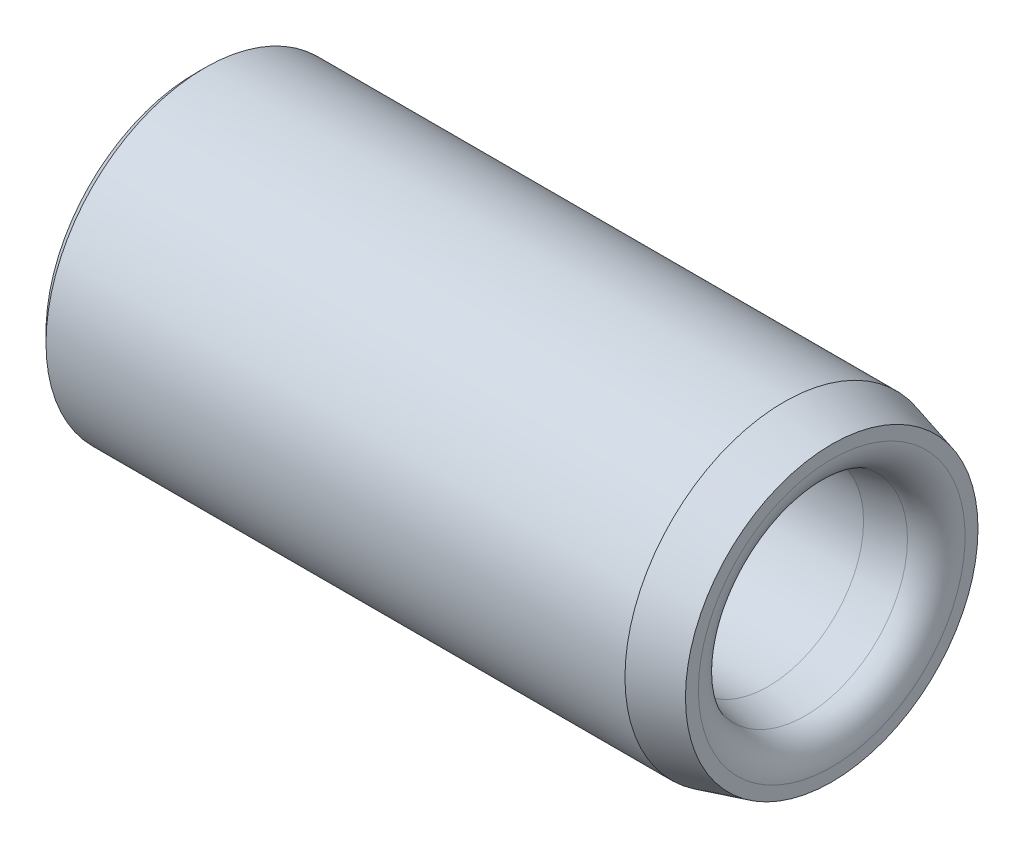
SolidWorks part; units mm, degrees
material "黄銅"
ref_plane "Front Plane" through (0, 0, 0) normal (0, 0, 1) x (1, 0, 0)
ref_plane "Top Plane" through (0, 0, 0) normal (0, 1, 0) x (1, 0, 0)
ref_plane "Right Plane" through (0, 0, 0) normal (1, 0, 0) x (0, 0, -1)
ref_axis "Axis_X" through (0, 0, 0) along (1, 0, 0)
ref_axis "Axis_Y" through (0, 0, 0) along (0, 1, 0)
ref_axis "Axis_Z" through (0, 0, 0) along (0, 0, 1)
sketch "Sketch1" plane through (0, 0, 0) normal (0, 0, 1) x (1, 0, 0)
  line L0 (0, 0) -> (20, 0) construction
  line L1 (0, 3) -> (0, 5)
  line L2 (0, 5) -> (20, 5)
  line L4 (20, 5) -> (20, 3)
  line L6 (20, 3) -> (0, 3)
  dimension "L" = 20
  dimension "D_s" = 6
  dimension "D" = 10
revolve "Revolve1" add sketch "Sketch1" angle 360 about L0
chamfer "Chamfer1" distance 0.3 angle 45 1 edges at (0, 0, 5)
chamfer "Chamfer2" distance 1.5 angle 15 1 edges at (20, 0, 5) first distance on face at (0.3, 0, -5)
chamfer "Chamfer3" distance 2 angle 10 2 edges at (0, 0, 3) (20, 0, 3) first distance on face at (20, 0, 3)
fillet "Fillet1" radius 1 2 edges at (0, 0, -3.3527) (20, 0, 3.3527)
